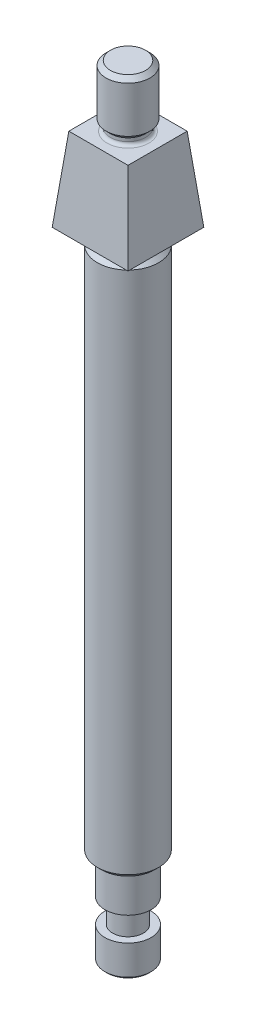
SolidWorks part; units mm, degrees
material "1.0050 (E295)"
ref_plane "Front Plane" through (0, 0, 0) normal (0, 0, 1) x (1, 0, 0)
ref_plane "Top Plane" through (0, 0, 0) normal (0, 1, 0) x (1, 0, 0)
ref_plane "Right Plane" through (0, 0, 0) normal (1, 0, 0) x (0, 0, -1)
sketch "Sketch1" plane through (0, 0, 0) normal (0, 1, 0) x (1, 0, 0)
  circle A0 centre (0, 0) radius 10.5
  dimension "D1" = 21
extrude "Boss-Extrude1" add sketch "Sketch1" along normal blind 42
sketch "Sketch3" plane through (0, 42, 0) normal (0, 1, 0) x (1, 0, 0)
  circle A0 centre (0, 0) radius 14
  dimension "D1" = 28
extrude "Boss-Extrude2" add sketch "Sketch3" along normal blind 243
sketch "Sketch4" plane through (0, 285, 0) normal (0, 1, 0) x (1, 0, 0)
  circle A0 centre (0, 0) radius 9
  dimension "D1" = 18
extrude "Boss-Extrude3" add sketch "Sketch4" along normal blind 5
sketch "Sketch5" plane through (0, 290, 0) normal (0, 1, 0) x (1, 0, 0)
  line L1 (-17.3, -17.3) -> (17.3, -17.3)
  line L2 (-17.3, -17.3) -> (-17.3, 17.3)
  line L3 (-17.3, 17.3) -> (17.3, 17.3)
  line L4 (17.3, -17.3) -> (17.3, 17.3)
  line L5 (-17.3, -17.3) -> (17.3, 17.3) construction
  line L6 (-17.3, 17.3) -> (17.3, -17.3) construction
  point P0 (0, 0)
  dimension "D1" = 34.6
  dimension "D2" = 34.6
extrude "Boss-Extrude4" add sketch "Sketch5" along normal blind 38 draft 5.711
sketch "Sketch6" plane through (0, 328, 0) normal (0, 1, 0) x (1, 0, 0)
  circle A0 centre (0, 0) radius 8
  dimension "D1" = 16
extrude "Boss-Extrude6" add sketch "Sketch6" along normal blind 3 contours A0
sketch "Sketch7" plane through (0, 331, 0) normal (0, 1, 0) x (1, 0, 0)
  circle A0 centre (0, 0) radius 10
  dimension "D1" = 20
extrude "Boss-Extrude7" add sketch "Sketch7" along normal blind 25
chamfer "Chamfer1" distance 2 angle 45 2 edges at (0, 331, 10) (0, 356, 10)
fillet "Fillet2" radius 2.5 2 edges at (0, 285, 9) (0, 290, 9)
sketch "Sketch8" plane through (0, 0, 0) normal (0, 0, 1) x (1, 0, 0)
  line L0 (-10.5, 42) -> (-10.5, 0) construction
  line L1 (-10.5, 25.5) -> (-7, 25.5)
  line L2 (-10.5, 25.5) -> (-10.5, 14.5)
  line L3 (-10.5, 14.5) -> (-7, 14.5)
  line L4 (-7, 25.5) -> (-7, 14.5)
  line L5 (-14, 42) -> (14, 42) construction
  point P6 (-10.5, 20)
  dimension "D1" = 11
  dimension "D2" = 7
  dimension "D3" = 22
revolve "Cut-Revolve1" cut sketch "Sketch8" angle 360 about axis through (0, 42, 0) along (0, -1, 0)
chamfer "Chamfer2" distance 2 angle 45 2 edges at (0, 42, 14) (0, 285, 14)
chamfer "Chamfer3" distance 1 angle 45 1 edges at (0, 0, 10.5)
fillet "Fillet3" radius 1.5 1 edges at (0, 328, 8)
equation "\"D3@Boss-Extrude4\"=atn(0.1)"
